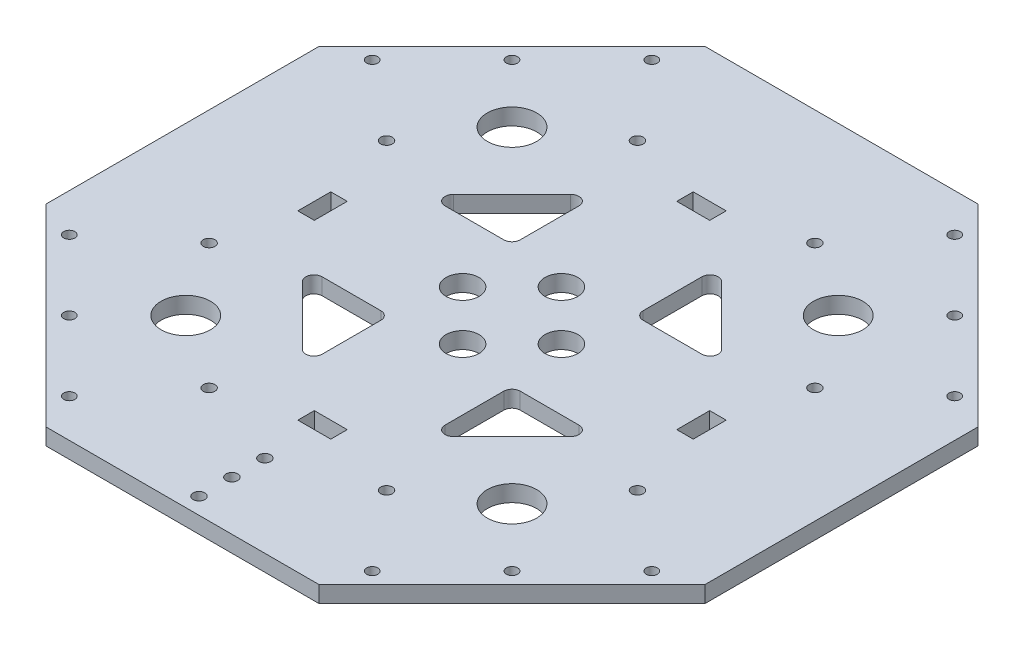
SolidWorks part; units mm, degrees
material "Custom Plastic"
ref_plane "Front Plane" through (0, 0, 0) normal (0, 0, 1) x (1, 0, 0)
ref_plane "Top Plane" through (0, 0, 0) normal (0, 1, 0) x (1, 0, 0)
ref_plane "Right Plane" through (0, 0, 0) normal (1, 0, 0) x (0, 0, -1)
ref_axis "Axis1" through (0, -0.2997, 0) along (0, 1, 0)
sketch "Base sketch" plane through (0, 0, 0) normal (0, 1, 0) x (1, 0, 0)
  line L1 (-127, 52.6051) -> (-127, -52.6051)
  line L2 (-127, -52.6051) -> (-52.6051, -127)
  line L3 (-52.6051, -127) -> (52.6051, -127)
  line L4 (52.6051, -127) -> (127, -52.6051)
  line L5 (127, -52.6051) -> (127, 52.6051)
  line L6 (127, 52.6051) -> (52.6051, 127)
  line L7 (52.6051, 127) -> (-52.6051, 127)
  line L8 (-52.6051, 127) -> (-127, 52.6051)
  circle A0 centre (0, 0) radius 127 construction
  dimension "D1" = 254
extrude "Base" add sketch "Base sketch" along normal blind 6.35
sketch "Sketch3" plane through (0, 6.35, 0) normal (0, 1, 0) x (1, 0, 0)
  line L0 (52.6051, 127) -> (-52.6051, 127) construction
  line L1 (-34.925, 114.3) -> (34.925, 114.3)
  line L2 (-34.925, 114.3) -> (-34.925, 79.375)
  line L4 (-34.925, 79.375) -> (34.925, 79.375)
  line L5 (34.925, 114.3) -> (34.925, 79.375)
  point P6 (0, 79.375)
  dimension "D1" = 69.85
  dimension "D2" = 34.925
  dimension "D3" = 12.7
sketch "Sketch4" plane through (0, 6.35, 0) normal (0, 1, 0) x (1, 0, 0)
  line L0 (0, 0) -> (0, 127) construction
  line L1 (52.6051, 127) -> (-52.6051, 127) construction
  line L4 (-6.35, 69.85) -> (6.35, 69.85)
  line L5 (-6.35, 69.85) -> (-6.35, 76.2)
  line L6 (-6.35, 76.2) -> (6.35, 76.2)
  line L7 (6.35, 69.85) -> (6.35, 76.2)
  line L8 (-6.35, 69.85) -> (6.35, 76.2) construction
  line L10 (-6.35, 76.2) -> (6.35, 69.85) construction
  point P5 (0, 73.025)
  dimension "D1" = 6.35
  dimension "D2" = 12.7
  dimension "D3" = 53.975
extrude "Support cutouts" cut sketch "Sketch4" against normal up to next
pattern_circular "Support cutout pattern" count 4 over 360 about axis through (0, -0.2997, 0) along (0, 1, 0) of "Support cutouts"
sketch "Sketch11" plane through (0, 6.35, 0) normal (0, 1, 0) x (1, 0, 0)
  line L1 (95.25, 39.4538) -> (39.4538, 95.25) construction
  line L2 (39.4538, 95.25) -> (-39.4538, 95.25) construction
  line L3 (-39.4538, 95.25) -> (-95.25, 39.4538) construction
  line L4 (-95.25, 39.4538) -> (-95.25, -39.4538) construction
  line L5 (-95.25, -39.4538) -> (-39.4538, -95.25) construction
  line L6 (-39.4538, -95.25) -> (39.4538, -95.25) construction
  line L7 (39.4538, -95.25) -> (95.25, -39.4538) construction
  line L8 (95.25, -39.4538) -> (95.25, 39.4538) construction
  line L9 (-34.1933, 82.55) -> (-82.55, 34.1933)
  line L10 (-82.55, 34.1933) -> (-82.55, -34.1933)
  line L11 (-82.55, -34.1933) -> (-34.1933, -82.55)
  line L12 (-34.1933, -82.55) -> (34.1933, -82.55)
  line L13 (34.1933, -82.55) -> (82.55, -34.1933)
  line L14 (82.55, -34.1933) -> (82.55, 34.1933)
  line L15 (82.55, 34.1933) -> (34.1933, 82.55)
  line L16 (34.1933, 82.55) -> (-34.1933, 82.55)
  circle A0 centre (0, 0) radius 95.25 construction
  circle A1 centre (0, 0) radius 82.55 construction
  dimension "D1" = 190.5
  dimension "D2" = 12.7
hole_wizard "#8 Clearance Hole1" positions "Sketch13" profile "Sketch12" hole size "#8" standard "ANSI Inch" end condition through all
sketch "Sketch13" plane through (0, 6.35, 0) normal (0, 1, 0) x (1, 0, 0)
  point P0 (-82.55, 34.1933)
  point P3 (-34.1933, 82.55)
  point P6 (34.1933, 82.55)
  point P9 (82.55, 34.1933)
  point P12 (82.55, -34.1933)
  point P15 (34.1933, -82.55)
  point P18 (-34.1933, -82.55)
  point P21 (-82.55, -34.1933)
sketch "Sketch12" plane through (-82.55, 6.35, -34.1933) normal (1, 0, 0) x (0, 0, 1)
  line L0 (0, 0) -> (0, 6.35)
  line L1 (0, 6.35) -> (2.2479, 6.35)
  line L2 (2.2479, 6.35) -> (2.2479, 0)
  line L5 (2.2479, 0) -> (0, 0)
  line L11 (0, -6.35) -> (0, 107.95) construction
  dimension "Thru Hole Dia." = 4.4958
  dimension "Thru Hole Depth" = 6.35
sketch "Sketch14" plane through (0, 6.35, 0) normal (0, 1, 0) x (1, 0, 0)
  circle A0 centre (-62.8618, 62.8618) radius 9.525
  circle A1 centre (62.8618, 62.8618) radius 9.525
  circle A2 centre (62.8618, -62.8618) radius 9.525
  circle A3 centre (-62.8618, -62.8618) radius 9.525
  point P13 (0, 0)
  dimension "D2" = 19.05
  dimension "D1" = 88.9
  dimension "D3" = 4
extrude "Cable holes" cut sketch "Sketch14" against normal up to next
sketch "Sketch15" plane through (0, 6.35, 0) normal (0, 1, 0) x (1, 0, 0)
  line L0 (0, -127) -> (0, 0) construction
  line L1 (-52.6051, -127) -> (52.6051, -127) construction
  point P5 (0, -120.65)
  point P6 (0, -107.95)
  point P7 (0, -95.25)
  dimension "D1" = 6.35
  dimension "D2" = 12.7
  dimension "D3" = 12.7
hole_wizard "#8 Clearance Hole2" positions "Sketch17" profile "Sketch16" hole size "#8" standard "ANSI Inch" end condition through all
sketch "Sketch17" plane through (0, 6.35, 0) normal (0, 1, 0) x (1, 0, 0)
  point P0 (0, -120.65)
  point P3 (0, -107.95)
  point P6 (0, -95.25)
sketch "Sketch16" plane through (0, 6.35, 120.65) normal (1, 0, 0) x (0, 0, 1)
  line L0 (0, 0) -> (0, 6.35)
  line L1 (0, 6.35) -> (2.2479, 6.35)
  line L2 (2.2479, 6.35) -> (2.2479, 0)
  line L5 (2.2479, 0) -> (0, 0)
  line L11 (0, -6.35) -> (0, 107.95) construction
  dimension "Thru Hole Dia." = 4.4958
  dimension "Thru Hole Depth" = 6.35
sketch "Sketch18" plane through (0, 6.35, 0) normal (0, 1, 0) x (1, 0, 0)
  line L0 (89.8026, 89.8026) -> (0, 0) construction
  line L1 (127, 52.6051) -> (52.6051, 127) construction
  line L2 (58.3717, 112.2532) -> (112.2532, 58.3717) construction
  point P7 (85.3124, 85.3124)
  dimension "D1" = 76.2
  dimension "D2" = 6.35
hole_wizard "plate mounting holes" positions "Sketch20" profile "Sketch19" hole size "#8" standard "ANSI Inch"
sketch "Sketch20" plane through (0, 6.35, 0) normal (0, 1, 0) x (1, 0, 0)
  line L0 (58.3717, 112.2532) -> (112.2532, 58.3717) construction
  point P0 (112.2532, 58.3717)
  point P3 (85.3124, 85.3124)
  point P7 (58.3717, 112.2532)
sketch "Sketch19" plane through (112.2532, 6.35, -58.3717) normal (1, 0, 0) x (0, 0, 1)
  line L0 (0, 0) -> (0, 6.351)
  line L1 (0, 6.351) -> (2.1526, 6.351)
  line L2 (2.1526, 6.351) -> (2.1526, 0)
  line L5 (2.1526, 0) -> (0, 0)
  line L10 (0, 6.351) -> (-2.1527, 6.351) construction
  line L11 (0, -6.35) -> (0, 107.95) construction
  dimension "Hole Dia." = 4.3053
  dimension "Hole Depth" = 6.351
  dimension "Drill Angle" = 180
pattern_circular "CirPattern1" count 4 over 360 about axis through (0, -0.2997, 0) along (0, 1, 0) of "plate mounting holes"
sketch "Sketch21" plane through (0, 6.35, 0) normal (0, 1, 0) x (1, 0, 0)
  line L0 (-6.35, 69.85) -> (6.35, 69.85) construction
  line L1 (-57.15, -23.6723) -> (-23.6723, -57.15)
  line L2 (-23.6723, -57.15) -> (23.6723, -57.15)
  line L3 (23.6723, -57.15) -> (57.15, -23.6723)
  line L4 (57.15, -23.6723) -> (57.15, 23.6723)
  line L5 (57.15, 23.6723) -> (23.6723, 57.15)
  line L6 (23.6723, 57.15) -> (-23.6723, 57.15)
  line L7 (-23.6723, 57.15) -> (-57.15, 23.6723)
  line L8 (-57.15, 23.6723) -> (-57.15, -23.6723)
  circle A0 centre (0, 0) radius 57.15 construction
  dimension "D1" = 114.3
extrude "Cut-Extrude1" cut sketch "Sketch21" against normal through all
sketch "Sketch24" plane through (0, 6.35, 0) normal (0, 1, 0) x (1, 0, 0)
  line L0 (-57.15, 23.6723) -> (-57.15, -23.6723) construction
  line L1 (-23.6723, 57.15) -> (23.6723, 57.15)
  line L2 (-23.6723, 57.15) -> (-23.6723, 23.6723)
  line L3 (-23.6723, -57.15) -> (23.6723, -57.15)
  line L4 (23.6723, 57.15) -> (23.6723, 23.6723)
  line L5 (57.15, -23.6723) -> (23.6723, -23.6723)
  line L6 (57.15, -23.6723) -> (57.15, 23.6723)
  line L7 (57.15, 23.6723) -> (23.6723, 23.6723)
  line L8 (-57.15, -23.6723) -> (-57.15, 23.6723)
  line L9 (-23.6723, 57.15) -> (-57.15, 23.6723) construction
  line L11 (23.6723, -23.6723) -> (23.6723, -57.15)
  line L12 (-23.6723, -23.6723) -> (-23.6723, -57.15)
  line L13 (-23.6723, 23.6723) -> (-57.15, 23.6723)
  line L14 (-23.6723, -23.6723) -> (-57.15, -23.6723)
extrude "Boss-Extrude1" add sketch "Sketch24" against normal through all
fillet "Fillet1" radius 3.175 12 edges at (-23.6723, 3.175, -23.6723) (23.6723, 3.175, 23.6723) (23.6723, 3.175, -23.6723) (-23.6723, 3.175, 23.6723) (-57.15, 3.175, 23.6723) (-23.6723, 3.175, 57.15) (23.6723, 3.175, 57.15) (57.15, 3.175, 23.6723) (57.15, 3.175, -23.6723) (23.6723, 3.175, -57.15) (-23.6723, 3.175, -57.15) (-57.15, 3.175, -23.6723)
sketch "Sketch26" plane through (0, 6.35, 0) normal (0, 1, 0) x (1, 0, 0)
  circle A0 centre (0, 19.05) radius 6.35
  dimension "D2" = 12.7
  dimension "D1" = 19.05
extrude "Cut-Extrude2" cut sketch "Sketch26" against normal through all
pattern_circular "CirPattern2" count 4 over 360 about axis through (0, -0.2997, 0) along (0, 1, 0) of "Cut-Extrude2"
equation "\"MAT_THICKNESS\"=0.25"
equation "\"D1@Base\"=\"MAT_THICKNESS\""
equation "\"D1@Sketch4\"=\"MAT_THICKNESS\""
